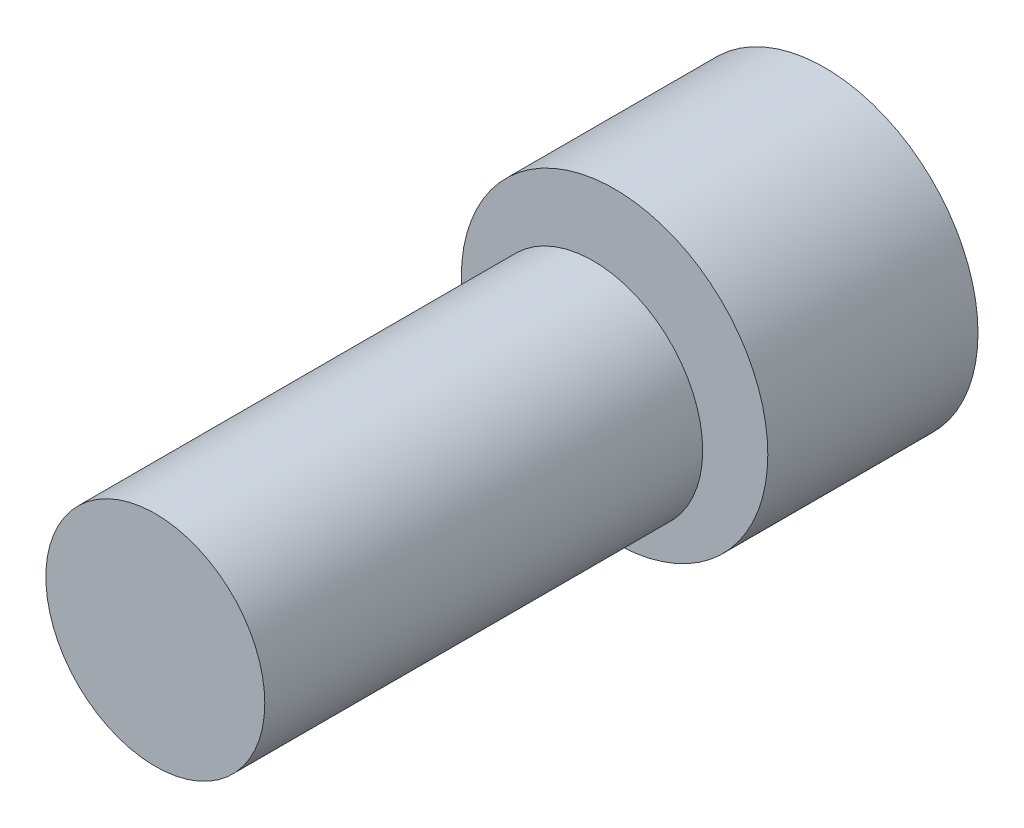
SolidWorks part; units mm, degrees
ref_plane "Front Plane" through (0, 0, 0) normal (0, 0, 1) x (1, 0, 0)
ref_plane "Top Plane" through (0, 0, 0) normal (0, 1, 0) x (1, 0, 0)
ref_plane "Right Plane" through (0, 0, 0) normal (1, 0, 0) x (0, 0, -1)
sketch "Sketch1" plane through (0, 0, 0) normal (0, 0, 1) x (1, 0, 0)
  line L0 (0, 0) -> (3.16, 0) construction
  line L1 (3.16, 0) -> (3.16, 4.317) construction
  line L2 (0, 0) -> (3.16, 4.317) construction
  circle A6 centre (2.0673, 2.8242) radius 3.5
  circle A8 centre (1.0927, 1.4928) radius 3.5 construction
  circle A9 centre (1.58, 2.1585) radius 2.5
  point P7 (1.0927, 1.4928)
  dimension "D1" = 3.16
  dimension "D4" = 7
  dimension "D2" = 7
  dimension "D3" = 5
extrude "Boss-Extrude1" add sketch "Sketch1" along normal blind 4.8 contours A6 A9 | A9 region at (-1.3337, 2.8242, 0) region at (1.58, 2.1585, 0)
extrude "Boss-Extrude2" add sketch "Sketch1<3>" along normal blind 14.8 contours A9
sketch "Sketch1<3>" plane through (0, 0, 0) normal (0, 0, 1) x (1, 0, 0) same geometry as "Sketch1"
